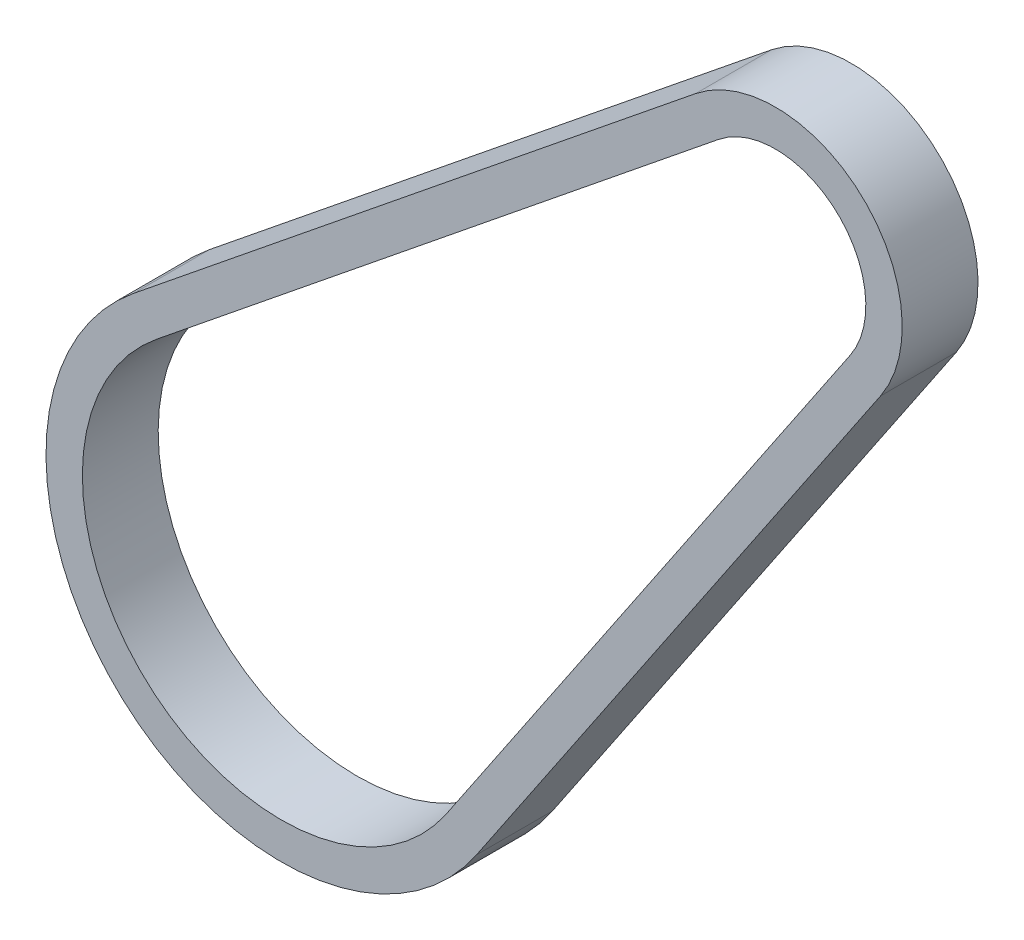
SolidWorks part; units mm, degrees
material "Rubber"
ref_plane "Front Plane" through (0, 0, 0) normal (0, 0, 1) x (1, 0, 0)
ref_plane "Top Plane" through (0, 0, 0) normal (0, 1, 0) x (1, 0, 0)
ref_plane "Right Plane" through (0, 0, 0) normal (1, 0, 0) x (0, 0, -1)
sketch "Sketch2" plane through (0, 0, 0) normal (0, 0, 1) x (1, 0, 0)
  line L0 (0, 0) -> (1, 0) construction
  line L1 (0, 0) -> (0, 1) construction
  line L2 (38.5283, 31.5331) -> (11.8777, -8.006)
  line L3 (-9.0016, 11.1421) -> (28.0887, 41.1072)
  arc A0 (28.0887, 41.1072) -> (38.5283, 31.5331) centre (32.5895, 35.5361) cw
  arc A1 (11.8777, -8.006) -> (-9.0016, 11.1421) centre (0, 0) cw
extrude "Extrude-Thin1" add sketch "Sketch2" against normal blind 5 thin thin type two direction wall 1.2 second wall 1.2
